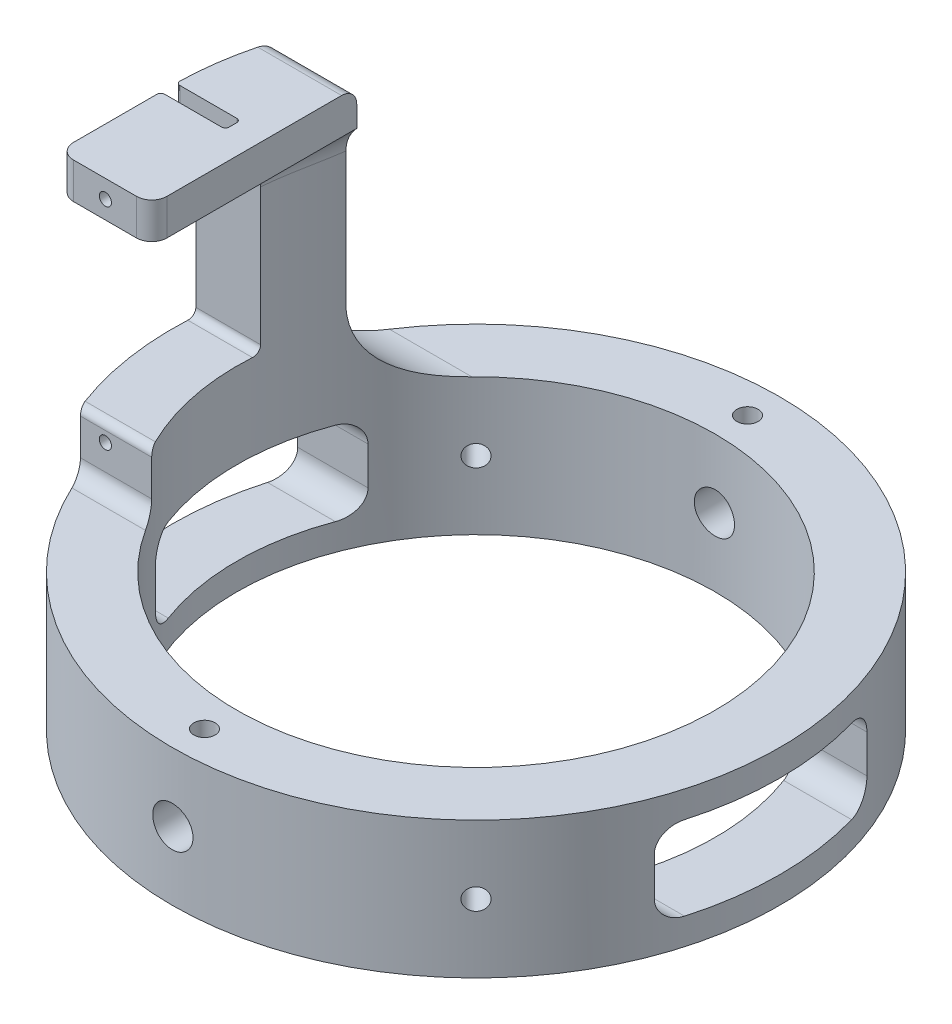
SolidWorks part; units mm, degrees
ref_plane "Plan de face" through (0, 0, 0) normal (0, 0, 1) x (1, 0, 0)
ref_plane "Plan de dessus" through (0, 0, 0) normal (0, 1, 0) x (1, 0, 0)
ref_plane "Plan de droite" through (0, 0, 0) normal (1, 0, 0) x (0, 0, -1)
sketch "Esquisse1" plane through (0, 0, 0) normal (0, 1, 0) x (1, 0, 0)
  circle A0 centre (0, 0) radius 40
  circle A1 centre (0, 0) radius 31.5
  dimension "D1" = 80
  dimension "D2" = 63
extrude "Boss.-Extru.1" add sketch "Esquisse1" along normal mid plane 18
sketch "Esquisse2" plane through (0, 9, 0) normal (0, 1, 0) x (1, 0, 0)
  line L0 (-38.1576, 12) -> (-29.1247, 12)
  line L1 (-37.081, -15) -> (-27.6993, -15)
  arc A0 (-38.1576, 12) -> (-37.081, -15) centre (0, 0) ccw
  arc A1 (-29.1247, 12) -> (-27.6993, -15) centre (0, 0) ccw
  circle A2 centre (0, 0) radius 40 construction
  circle A3 centre (0, 0) radius 31.5 construction
  dimension "D1" = 12
  dimension "D2" = 15
extrude "Boss.-Extru.2" add sketch "Esquisse2" along normal blind 35.5
ref_plane "Plan1" through (0, 0, 40) normal (0, 0, 1) x (1, 0, 0)
sketch "Esquisse3" plane through (0, 0, 40) normal (0, 0, 1) x (1, 0, 0)
  circle A0 centre (0, 0) radius 2.65
  dimension "D1" = 5.3
extrude "Enlèv. mat.-Extru.1" cut sketch "Esquisse3" against normal up to next
sketch "Esquisse5" plane through (0, 9, 0) normal (0, 1, 0) x (1, 0, 0)
  line L0 (0, -31.5) -> (0, -40) construction
  circle A0 centre (0, -35.75) radius 1.4
  arc A1 (-27.6993, -15) -> (-29.1247, 12) centre (0, 0) ccw construction
  arc A2 (-37.081, -15) -> (-38.1576, 12) centre (0, 0) ccw construction
  dimension "D1" = 2.8
extrude "Enlèv. mat.-Extru.3" cut sketch "Esquisse5" against normal up to next
mirror "Symétrie1" about plane through (0, 0, 0) normal (0, 0, 1) of "Enlèv. mat.-Extru.3", "Enlèv. mat.-Extru.1"
ref_plane "Plan2" through (28.2843, 0, 28.2843) normal (0.7071, 0, 0.7071) x (0, -1, 0)
sketch "Esquisse4" plane through (28.2843, 0, 28.2843) normal (0.7071, 0, 0.7071) x (0, -1, 0)
  circle A0 centre (0, 0) radius 1.4
  dimension "D1" = 2.8
extrude "Enlèv. mat.-Extru.2" cut sketch "Esquisse4" against normal up to next
pattern_circular "Répétition circulaire1" count 4 over 360 about axis through (0, 9, 0) along (0, -1, 0) of "Enlèv. mat.-Extru.2"
ref_plane "Plan3" through (-40, 0, 0) normal (-1, 0, 0) x (0, 0, 1)
sketch "Esquisse6" plane through (-40, 0, 0) normal (-1, 0, 0) x (0, 0, 1)
  line L0 (15, 44.5) -> (15, 9) construction
  line L1 (15, 39.75) -> (-3, 39.75)
  line L2 (15, 39.75) -> (15, 16.75)
  line L3 (15, 16.75) -> (-3, 16.75)
  line L4 (-3, 39.75) -> (-3, 16.75)
  line L6 (31.5, 9) -> (-31.5, 9) construction
  dimension "D1" = 23
  dimension "D2" = 7.75
  dimension "D3" = 18
extrude "Enlèv. mat.-Extru.4" cut sketch "Esquisse6" against normal up to next
sketch "Esquisse7" plane through (0, 44.5, 0) normal (0, 1, 0) x (1, 0, 0)
  line L0 (-27.6993, -15) -> (-39.8993, -15) construction
  line L2 (-40, 0) -> (-40, -15)
  line L3 (-40, -15) -> (-27.6993, -15)
  line L4 (-27.6993, 12) -> (-27.6993, -15)
  line L5 (-27.6993, 1.5) -> (-27.6993, -15) construction
  line L6 (-29.1247, 12) -> (-38.1576, 12) construction
  line L7 (-27.6993, 12) -> (-38.1576, 12)
  arc A0 (-38.1576, 12) -> (-37.081, -15) centre (0, 0) ccw construction
  arc A1 (-37.081, -15) -> (-38.1576, 12) centre (0, 0) ccw construction
  arc A2 (-38.1576, 12) -> (-40, 0) centre (0, 0) ccw
extrude "Boss.-Extru.3" add sketch "Esquisse7" against normal blind 4.75
sketch "Esquisse9" plane through (0, 44.5, 0) normal (0, 1, 0) x (1, 0, 0)
  line L0 (-31.3568, 3) -> (-39.8873, 3) construction
  line L1 (-31.5, 0.5) -> (-40, 0.5)
  line L2 (-31.5, 0.5) -> (-31.5, -1.5)
  line L3 (-31.5, -1.5) -> (-40, -1.5)
  line L4 (-40, 0.5) -> (-40, -1.5)
  line L5 (-40, 0) -> (-40, -15) construction
  dimension "D2" = 2
  dimension "D3" = 2.5
  dimension "D4" = 8.5
extrude "Enlèv. mat.-Extru.6" cut sketch "Esquisse9" against normal up to next
sketch "Esquisse8" plane through (0, 0, 15) normal (0, 0, 1) x (1, 0, 0)
  circle A0 centre (-33.7993, 42.125) radius 0.8
  circle A1 centre (-33.7993, 14.375) radius 0.8
  dimension "D1" = 1.6
extrude "Enlèv. mat.-Extru.5" cut sketch "Esquisse8" against normal blind 5
sketch "Esquisse10" plane through (0, 0, 0) normal (1, 0, 0) x (0, 0, -1)
  line L1 (-14, -5.5) -> (14, -5.5)
  line L2 (-14, -5.5) -> (-14, 5.5)
  line L3 (-14, 5.5) -> (14, 5.5)
  line L4 (14, -5.5) -> (14, 5.5)
  line L5 (-14, -5.5) -> (14, 5.5) construction
  line L6 (-14, 5.5) -> (14, -5.5) construction
  point P0 (0, 0)
  dimension "D1" = 28
  dimension "D2" = 11
extrude "Enlèv. mat.-Extru.7" cut sketch "Esquisse10" against normal mid plane 100
fillet "Congé6" radius 0.5 4 edges at (-31.5, 42.125, 1.5) (-31.5, 42.125, -0.5) (-40, 42.125, 1.5) (-39.9969, 42.125, -0.5)
fillet "Congé1" radius 10 1 edges at (-33.6411, 9, -12)
fillet "Congé3" radius 4 1 edges at (-30.5738, 39.75, -7.5826)
fillet "Congé2" radius 2 4 edges at (-32.9284, 44.5, -12) (-27.6993, 42.125, 15) (-40, 42.125, 15) (-32.3901, 9, 15)
fillet "Congé5" radius 1 3 edges at (-33.7933, 39.75, -3) (-35.6221, 16.75, -3) (-32.3901, 16.75, 15)
fillet "Congé7" radius 3 8 edges at (32.8439, -5.5, -14) (-32.8439, -5.5, -14) (32.8439, -5.5, 14) (-32.8439, -5.5, 14) (-32.8439, 5.5, 14) (32.8439, 5.5, 14) (32.8439, 5.5, -14) (-32.8439, 5.5, -14)
